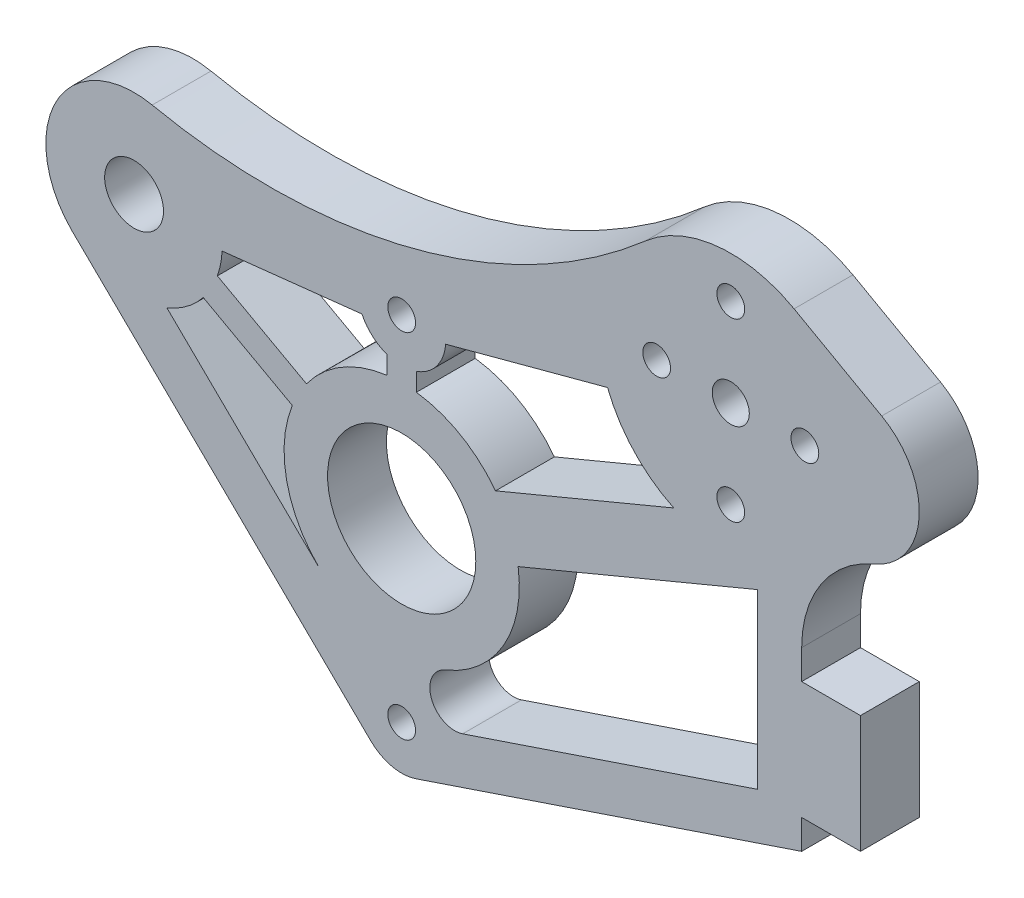
SolidWorks part; units mm, degrees
ref_plane "Front Plane" through (0, 0, 0) normal (0, 0, 1) x (1, 0, 0)
ref_plane "Top Plane" through (0, 0, 0) normal (0, 1, 0) x (1, 0, 0)
ref_plane "Right Plane" through (0, 0, 0) normal (1, 0, 0) x (0, 0, -1)
sketch "Sketch1" plane through (0, 0, 0) normal (0, 0, 1) x (1, 0, 0)
  line L0 (0, 19.05) -> (0, -19.05) construction
  line L1 (0, -55) -> (0, 55) construction
  line L2 (43.18, 6.35) -> (49.53, 6.35)
  line L3 (43.18, 6.35) -> (43.18, -6.35) construction
  line L4 (43.18, -6.35) -> (49.53, -6.35)
  line L5 (49.53, 6.35) -> (49.53, -6.35)
  line L6 (27.5266, 28.575) -> (43.5266, 28.575) construction
  line L7 (35.5266, 38.075) -> (35.5266, 19.075) construction
  line L8 (43.18, 6.35) -> (43.18, 9.525)
  line L9 (43.18, -6.35) -> (43.18, -9.525)
  line L10 (-35.5531, 9.066) -> (-3.3303, -22.4545)
  line L11 (43.18, -9.525) -> (1.5208, -23.5631)
  line L12 (55.88, -1000) -> (55.88, 49000) construction
  line L13 (51.8182, 35.5019) -> (42.3625, 40.7926)
  circle A0 centre (0, 19.05) radius 1.5
  circle A1 centre (0, -19.05) radius 1.5
  circle A2 centre (30.48, 0) radius 25.4 construction
  circle A3 centre (-30.48, 0) radius 25.4 construction
  circle A4 centre (-28.8925, 15.875) radius 38.1 construction
  circle A5 centre (0, 0) radius 8
  circle A6 centre (35.5266, 38.075) radius 1.5
  circle A7 centre (43.5266, 28.575) radius 1.5
  circle A8 centre (35.5266, 19.075) radius 1.5
  circle A9 centre (27.5266, 28.575) radius 1.5
  arc A10 (42.3625, 40.7926) -> (26.3164, 39.1189) centre (35.5266, 28.575) ccw
  circle A11 centre (-28.8925, 15.875) radius 3.175
  arc A12 (-26.9386, 25.1974) -> (-35.5531, 9.066) centre (-28.8925, 15.875) ccw
  arc A14 (0, 12.7) -> (-1.3323, 25.2587) centre (0, 19.05) ccw construction
  arc A15 (43.18, 9.525) -> (50.9954, 21.2481) centre (55.88, 9.525) cw
  arc A16 (50.9954, 21.2481) -> (51.8182, 35.5019) centre (47.9425, 28.575) ccw
  arc A17 (-26.9386, 25.1974) -> (26.3164, 39.1189) centre (-14.2798, 85.5939) ccw
  arc A19 (46.4173, 19.7778) -> (42.3625, 40.7926) centre (35.5266, 28.575) ccw construction
  arc A20 (26.3164, 39.1189) -> (22.2813, 24.0404) centre (35.5266, 28.575) ccw construction
  arc A21 (22.2813, 24.0404) -> (46.4173, 19.7778) centre (35.5266, 28.575) ccw construction
  arc A23 (-35.5531, 9.066) -> (-26.9386, 25.1974) centre (-28.8925, 15.875) ccw construction
  arc A24 (-1.3323, 25.2587) -> (0, 12.7) centre (0, 19.05) ccw construction
  arc A28 (-3.3303, -22.4545) -> (1.5208, -23.5631) centre (0, -19.05) ccw
  circle A31 centre (35.5266, 28.575) radius 2
  point P4 (0, 0)
  point P10 (49.53, 0)
  point P13 (-30.48, -25.4)
  point P24 (-28.8925, -22.225)
  point P26 (35.5266, 28.575)
  point P29 (35.5266, 28.575)
  point P37 (0, 0)
  point P39 (50.9291, 36.2082)
  point P41 (0, 0)
  point P50 (0, 0)
  dimension "D2" = 3
  dimension "D7" = 50.8
  dimension "D8" = 76.2
  dimension "D11" = 16
  dimension "D13" = 3
  dimension "D14" = 28
  dimension "D16" = 6.35
  dimension "D17" = 19.05
  dimension "D21" = 4.7625
  dimension "D22" = 12.7
  dimension "D25" = 12.7
  dimension "D26" = 4
  dimension "D1" = 38.1
  dimension "D3" = 12.7
  dimension "D4" = 6.35
  dimension "D5" = 43.18
  dimension "D6" = 30.48
  dimension "D9" = 3.175
  dimension "D10" = 19
  dimension "D12" = 16
  dimension "D15" = 1.5875
  dimension "D18" = 65.659
  dimension "D19" = 22.225
  dimension "D20" = 3.175
extrude "Boss-Extrude1" add sketch "Sketch1" along normal mid plane 6.35 contours L10 A28 L11 L9 L4 L5 L2 L8 A15 A16 L13 A10 A17 A12 A0 A1 A6 A7 A8 A9 A11 region at (12.9745, 9.6956, 0)
sketch "Sketch2" plane through (0, 0, 3.175) normal (0, 0, 1) x (1, 0, 0)
  line L0 (-20.5446, 11.2882) -> (-11.1305, 6.1157) construction
  line L1 (0, 12.7) -> (0, 19.05) construction
  line L2 (-4.734, 18.5298) -> (-19.4245, 16.9154) construction
  line L3 (-4.2899, 16.9815) -> (-19.3835, 15.3229)
  line L4 (-19.8969, 12.7437) -> (-10.2788, 7.459)
  line L5 (-1.5875, 12.6004) -> (-1.5875, 14.5599)
  line L6 (-19.4245, 16.9154) -> (-28.8925, 15.875) construction
  line L7 (0, 19.05) -> (-28.8925, 15.875) construction
  line L8 (-19.3835, 15.3229) -> (-23.7231, 14.846) construction
  line L9 (-1.5875, 17.2785) -> (-23.7231, 14.846) construction
  line L10 (-23.7231, 14.846) -> (-19.8969, 12.7437) construction
  line L11 (-23.7231, 14.846) -> (-1.5875, 2.6836) construction
  line L12 (-28.8925, 15.875) -> (-20.5446, 11.2882) construction
  line L13 (-28.8925, 15.875) -> (0, 0) construction
  line L14 (0, 19.05) -> (-4.734, 18.5298) construction
  line L15 (-1.5875, 17.2785) -> (-4.2899, 16.9815) construction
  line L16 (-1.5875, 14.5599) -> (-1.5875, 17.2785) construction
  line L17 (-1.5875, 2.6836) -> (-1.5875, 17.2785) construction
  line L18 (0, 0) -> (0, 12.7) construction
  line L19 (0, 0) -> (0, 19.05) construction
  line L20 (-1.5875, 2.6836) -> (-1.5875, 12.6004) construction
  line L21 (-10.2788, 7.459) -> (-1.5875, 2.6836) construction
  line L22 (-11.1305, 6.1157) -> (0, 0) construction
  line L23 (-11.8077, 4.6764) -> (-21.4258, 9.9611)
  line L24 (-25.3512, 7.0328) -> (-8.8808, -9.0786)
  line L25 (40.6577, 18.7181) -> (42.8568, 14.4937) construction
  line L26 (38.4175, 14.583) -> (38.4175, -6.1042)
  line L27 (43.18, -6.35) -> (43.18, -9.525) construction
  line L28 (38.4175, -6.1042) -> (6.5852, -16.8309)
  line L29 (43.18, -9.525) -> (1.5208, -23.5631) construction
  line L30 (1.5875, 12.6004) -> (1.5875, 14.5599)
  line L31 (0, 19.05) -> (35.5266, 28.575) construction
  line L32 (4.7481, 18.6794) -> (22.223, 23.3646)
  line L33 (0.4111, 17.5167) -> (35.9377, 27.0417) construction
  line L34 (50.9954, 21.2481) -> (0, 0) construction
  line L35 (38.4175, 19.4469) -> (10.1297, 7.6603)
  line L36 (38.4175, 12.5677) -> (12.572, 1.7987)
  line L37 (51.2197, 17.9019) -> (1.2212, -2.9308) construction
  line L38 (48.7773, 23.7635) -> (-1.2212, 2.9308) construction
  line L39 (49.9985, 20.8327) -> (0, 0) construction
  line L40 (-35.5531, 9.066) -> (-3.3303, -22.4545) construction
  line L41 (46.1247, 25.2334) -> (50.6668, 23.8013) construction
  line L42 (46.1247, 31.9166) -> (50.6668, 33.3487) construction
  line L43 (41.4973, 37.9472) -> (44.0562, 41.9638) construction
  line L44 (35.5266, 28.575) -> (41.4973, 37.9472) construction
  line L45 (35.5266, 28.575) -> (46.1247, 31.9166) construction
  line L46 (35.5266, 28.575) -> (46.1247, 25.2334) construction
  line L47 (35.5266, 28.575) -> (40.6577, 18.7181) construction
  line L48 (43.5266, 28.575) -> (42.8032, 30.8693) construction
  line L49 (43.5266, 28.575) -> (42.8032, 26.2807) construction
  arc A0 (-1.5875, 12.6004) -> (-10.2788, 7.459) centre (0, 0) ccw
  arc A1 (-4.2899, 16.9815) -> (-1.5875, 14.5599) centre (0, 19.05) ccw
  arc A2 (-19.8969, 12.7437) -> (-19.3835, 15.3229) centre (-28.8925, 15.875) ccw
  arc A3 (-19.4245, 16.9154) -> (-20.5446, 11.2882) centre (-28.8925, 15.875) ccw construction
  arc A4 (0, 14.2875) -> (-4.734, 18.5298) centre (0, 19.05) ccw construction
  arc A5 (-1.5875, 14.5599) -> (0, 14.2875) centre (0, 19.05) ccw construction
  arc A6 (-4.734, 18.5298) -> (-4.2899, 16.9815) centre (0, 19.05) ccw construction
  arc A7 (-11.1305, 6.1157) -> (0, 12.7) centre (0, 0) ccw construction
  arc A8 (-10.2788, 7.459) -> (-11.1305, 6.1157) centre (0, 0) ccw construction
  arc A9 (0, 12.7) -> (-1.5875, 12.6004) centre (0, 0) ccw construction
  arc A10 (-20.5446, 11.2882) -> (-19.8969, 12.7437) centre (-28.8925, 15.875) ccw construction
  arc A11 (-19.3835, 15.3229) -> (-19.4245, 16.9154) centre (-28.8925, 15.875) ccw construction
  arc A12 (-25.3512, 7.0328) -> (-21.4258, 9.9611) centre (-28.8925, 15.875) ccw
  arc A13 (-11.8077, 4.6764) -> (-8.8808, -9.0786) centre (0, 0) ccw
  arc A15 (22.223, 23.3646) -> (38.4175, 14.583) centre (35.5266, 28.575) ccw
  arc A16 (4.7262, -11.7878) -> (6.5852, -16.8309) centre (5.7267, -14.2832) ccw
  circle A17 centre (0, -19.05) radius 4.7625 construction
  arc A18 (1.5875, 12.6004) -> (4.7262, -11.7878) centre (0, 0) cw
  arc A19 (4.7481, 18.6794) -> (1.5875, 14.5599) centre (0, 19.05) cw
  arc A20 (38.4175, 14.583) -> (21.7264, 24.8751) centre (35.5266, 28.575) ccw construction
  arc A21 (21.7264, 24.8751) -> (22.223, 23.3646) centre (35.5266, 28.575) ccw construction
  arc A22 (44.0562, 41.9638) -> (50.6668, 33.3487) centre (35.5266, 28.575) cw construction
  arc A23 (46.1247, 31.9166) -> (41.4973, 37.9472) centre (35.5266, 28.575) ccw construction
  arc A24 (42.8568, 14.4937) -> (50.6668, 23.8013) centre (35.5266, 28.575) ccw construction
  arc A25 (40.6577, 18.7181) -> (46.1247, 25.2334) centre (35.5266, 28.575) ccw construction
  dimension "D1" = 19.05
  dimension "D2" = 25.4
  dimension "D3" = 9.525
  dimension "D7" = 28.575
  dimension "D10" = 1.5875
  dimension "D6" = 15.875
  dimension "D14" = 11.1125
  dimension "D5" = 1.5875
  dimension "D8" = 4.7625
  dimension "D9" = 4.7625
  dimension "D15" = 45
  dimension "D16" = 40
  dimension "D17" = 35
  dimension "D4" = 1.5875
  dimension "D11" = 1.5875
  dimension "D12" = 3.175
  dimension "D13" = 3.175
extrude "Cut-Extrude1" cut sketch "Sketch2" against normal through all contours A2 L4 A0 L5 A1 L3 | A13 L23 A12 L24 | L32 A19 L30 A18 L35 L26 A15 | L36 A18 A16 L28 L26 | A23 L42 A22 L43 | A25 L25 A24 L41 region at (-10.6919, 13.0465, 3.175) region at (-17.2678, 3.175, 3.175) region at (23.644, -2.8614, 3.175) region at (14.7528, 15.6802, 3.175)
